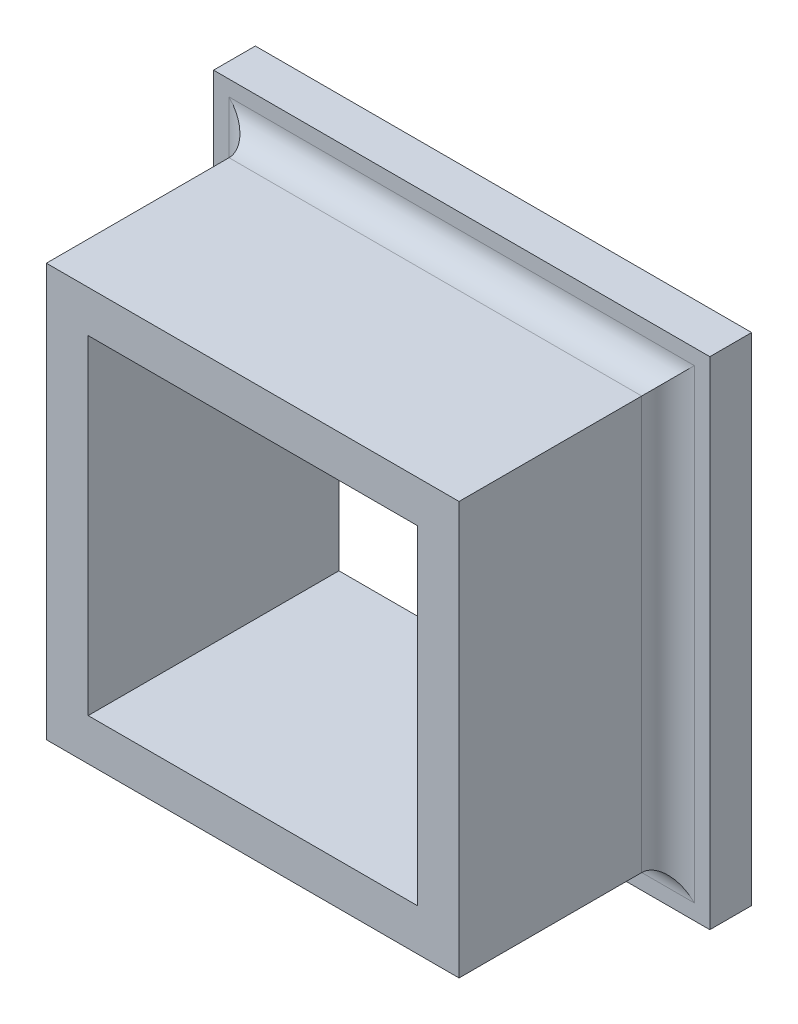
SolidWorks part; units mm, degrees
material "ABS"
ref_plane "Front Plane" through (0, 0, 0) normal (0, 0, 1) x (1, 0, 0)
ref_plane "Top Plane" through (0, 0, 0) normal (0, 1, 0) x (1, 0, 0)
ref_plane "Right Plane" through (0, 0, 0) normal (1, 0, 0) x (0, 0, -1)
sketch "Sketch1" plane through (0, 0, 0) normal (0, 0, 1) x (1, 0, 0)
  line L0 (-7.9925, 7.5534) -> (7.6825, 7.5534)
  line L1 (-6.405, 5.9659) -> (6.095, 5.9659)
  line L2 (-6.405, 5.9659) -> (-6.405, -6.5341)
  line L3 (-6.405, -6.5341) -> (6.095, -6.5341)
  line L4 (6.095, 5.9659) -> (6.095, -6.5341)
  line L5 (7.6825, 7.5534) -> (7.6825, -8.1216)
  line L6 (-7.9925, -8.1216) -> (7.6825, -8.1216)
  line L7 (-7.9925, 7.5534) -> (-7.9925, -8.1216)
  line L8 (-9.58, 9.1409) -> (9.27, 9.1409)
  line L13 (9.27, 9.1409) -> (9.27, -9.7091)
  line L14 (-9.58, -9.7091) -> (9.27, -9.7091)
  line L15 (-9.58, 9.1409) -> (-9.58, -9.7091)
  dimension "D1" = 12.5
  dimension "D2" = 12.5
  dimension "D3" = 1.5875
  dimension "D4" = 1.5875
extrude "Boss-Extrude2" add sketch "Sketch1" along normal blind 9.525 contours L0 L7 L6 L5 L1 L4 L3 L2 region at (-0.155, 7.3317, 0)
extrude "Boss-Extrude3" add sketch "Sketch1<7>" along normal blind 1.5875 contours L13 L14 L15 L8
sketch "Sketch1<7>" plane through (0, 0, 0) normal (0, 0, 1) x (1, 0, 0) same geometry as "Sketch1"
extrude "Cut-Extrude3" cut sketch "Sketch1<8>" along normal through all contours L4 L3 L2 L1
sketch "Sketch1<8>" plane through (0, 0, 0) normal (0, 0, 1) x (1, 0, 0) same geometry as "Sketch1"
fillet "Fillet4" radius 1 4 edges at (7.6825, -0.2841, 1.5875) (-0.155, 7.5534, 1.5875) (-0.155, -8.1216, 1.5875) (-7.9925, -0.2841, 1.5875)
